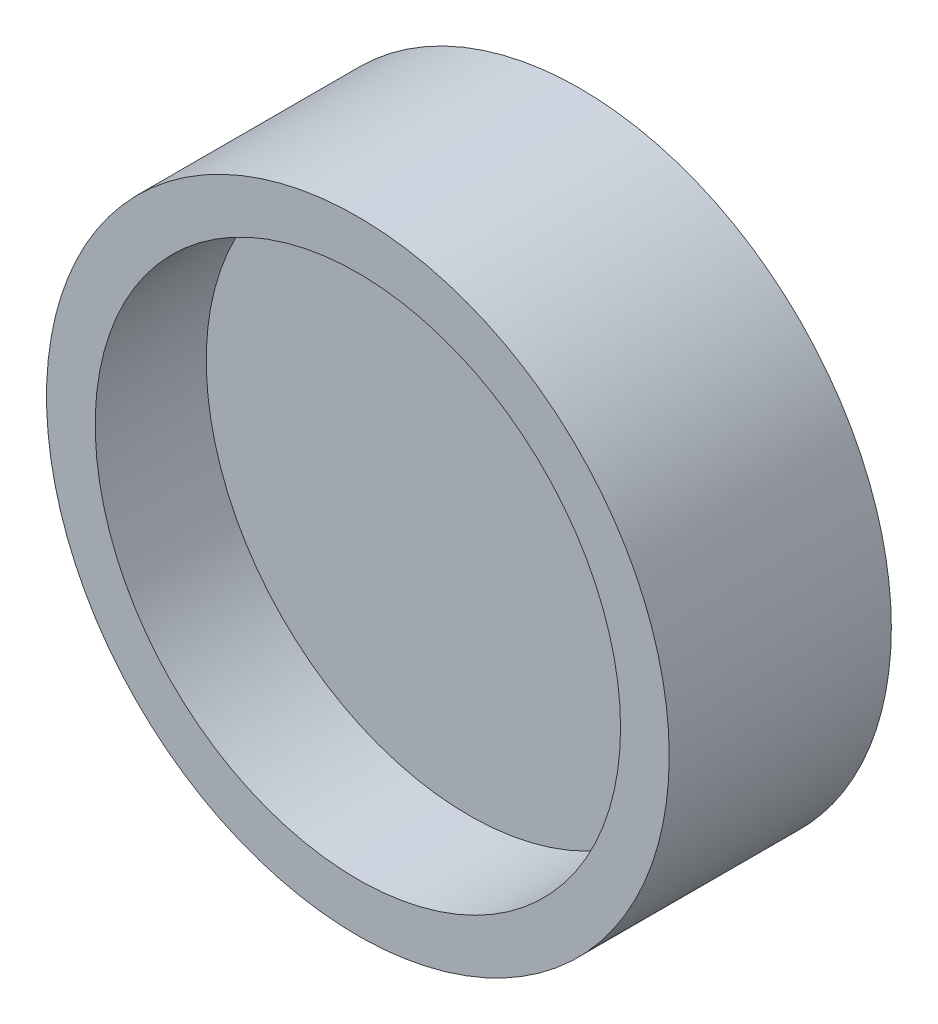
SolidWorks part; units mm, degrees
ref_plane "Front Plane" through (0, 0, 0) normal (0, 0, 1) x (1, 0, 0)
ref_plane "Top Plane" through (0, 0, 0) normal (0, 1, 0) x (1, 0, 0)
ref_plane "Right Plane" through (0, 0, 0) normal (1, 0, 0) x (0, 0, -1)
sketch "Body Circle" plane through (0, 0, 0) normal (0, 0, 1) x (1, 0, 0)
  line L0 (0, -24.95) -> (0, 24.95) construction
  circle A0 centre (0, 0) radius 24.95
  point P14 (0, 0)
extrude "Body" add sketch "Body Circle" along normal blind 17.8 contours A0
sketch "Inner Face Circle Sketch" plane through (0, 0, 17.8) normal (0, 0, 1) x (1, 0, 0)
  circle A0 centre (0, 0) radius 21.05
extrude "Inner Face" cut sketch "Inner Face Circle Sketch" against normal blind 8.9
sketch "Back Circle Sketch" plane through (0, 0, 0) normal (0, 0, -1) x (-1, 0, 0)
  line L0 (0, -26.5965) -> (0, 26.5965) construction
  line L1 (0, -19.9374) -> (-15, -19.9374) construction
  line L2 (-15, -19.9374) -> (-21.098, -13.3182) construction
  line L3 (-36.098, -33.2556) -> (0, 0) construction
  line L4 (-1.672, -23.3354) -> (-23.394, 0.2432) construction
  line L5 (-21.098, -13.3182) -> (-15.582, -8.2365)
  line L6 (11.5, 8.45) -> (0, 8.45) construction
  line L7 (-15, -19.9374) -> (-9.484, -14.8557)
  line L8 (-28.3873, 24.95) -> (28.3873, 24.95) construction
  line L9 (2.8283, -22.2891) -> (2.8283, -24.7891)
  line L10 (-2.8283, -22.2891) -> (-2.8283, -24.7891)
  line L11 (-32.3874, 0) -> (32.3874, 0) construction
  line L12 (2.8283, 22.2891) -> (2.8283, 24.7891)
  line L13 (-2.8283, 22.2891) -> (-2.8283, 24.7891)
  arc A0 (-15, -19.9374) -> (-2.8283, -24.7891) centre (0, 0) ccw
  circle A1 centre (0, 0) radius 24.95 construction
  arc A2 (-9.484, -14.8557) -> (-15.582, -8.2365) centre (-12.533, -11.5461) ccw
  circle A3 centre (11.5, 8.45) radius 4.5
  arc A4 (2.8283, -22.2891) -> (-2.8283, -22.2891) centre (0, -22.2891) ccw
  arc A5 (2.8283, -24.7891) -> (2.8283, 24.7891) centre (0, 0) ccw
  circle A6 centre (6.5, -13.95) radius 6.5
  arc A7 (2.8283, 22.2891) -> (-2.8283, 22.2891) centre (0, 22.2891) cw
  arc A8 (-2.8283, 24.7891) -> (-21.098, -13.3182) centre (0, 0) ccw
  point P8 (0, 0)
  point P14 (-18.049, -16.6278)
  point P16 (-12.533, -11.5461)
  point P24 (0, 24.95)
  point P35 (0, 0)
  point P42 (-23.6326, 0)
  point P44 (-21.8205, 0)
  point P45 (-22.2388, 0)
  dimension "D4" = 11.5
  dimension "D6" = 9
  dimension "D7" = 6.5
  dimension "D1" = 15
  dimension "D2" = 9
  dimension "D3" = 7.5
  dimension "D5" = 16.5
  dimension "D8" = 38.9
extrude "Back" add sketch "Back Circle Sketch" along normal blind 1.5
sketch "Rectangle Hole Sketch" plane through (0, 0, -1.5) normal (0, 0, -1) x (-1, 0, 0)
  line L8 (0, 0) -> (-28.5549, -26.3064) construction
  line L10 (-9.484, -14.8557) -> (-15, -19.9374) construction
  line L11 (-17.3135, -15.9502) -> (-14.6033, -18.8921)
  line L12 (-14.6033, -18.8921) -> (-13.5001, -17.8758)
  line L13 (-13.5001, -17.8758) -> (-16.2103, -14.9339)
  line L14 (-16.2103, -14.9339) -> (-17.3135, -15.9502)
  arc A1 (-9.484, -14.8557) -> (-15.582, -8.2365) centre (-12.533, -11.5461) ccw construction
  dimension "D1" = 1.5
  dimension "D2" = 4
  dimension "D3" = 5
extrude "Rectangle Hole" cut sketch "Rectangle Hole Sketch" against normal blind 5
pattern_circular "Rectangle Hole Pattern" count 4 over 360 about axis through (0, 0, 17.8) along (0, 0, -1) of "Rectangle Hole"
chamfer "Back Chamfer" distance 1.5 angle 60 7 edges at (-24.95, 0, -1.5) (-16, 8.45, -1.5) (9.2384, -23.1766, -1.5) (12.242, -17.3966, -1.5) (9.2234, -8.4971, -1.5) (18.34, -10.7773, -1.5) (22.498, 10.7861, -1.5) first distance on face at (24.95, 0, 17.8) first distance on face at (-16.913, -15.4068, -1.5) first distance on face at (12.242, -17.3966, -0.75) first distance on face at (10.8782, -10.0216, -0.75) first distance on face at (18.34, -10.7773, -0.75)
sketch "Alarm Switch Slot Sketch" plane through (0, 0, 0) normal (0, 0, 1) x (1, 0, 0)
  line L0 (-36.0088, 0) -> (36.0088, 0) construction
  line L1 (23.7482, -7.65) -> (23.7482, 7.65) construction
  line L2 (0, 0) -> (23.7482, 7.65) construction
  line L3 (0, 0) -> (23.7482, -7.65) construction
  line L4 (23.7482, 7.65) -> (21.2753, 6.8534)
  line L5 (23.7482, -7.65) -> (21.2753, -6.8534)
  arc A1 (21.098, -13.3182) -> (2.8283, 24.7891) centre (0, 0) ccw construction
  arc A2 (23.7482, 7.65) -> (23.7482, -7.65) centre (0, 0) cw
  arc A3 (21.2753, 6.8534) -> (21.2753, -6.8534) centre (0, 0) cw
  arc A4 (20.3976, -9.1403) -> (17.6671, 13.6924) centre (0, 0) ccw construction
  point P4 (0, 0)
  point P8 (23.7482, 0)
  point P14 (24.95, 0)
  point P18 (22.3519, 0)
  dimension "D1" = 7.65
extrude "Alarm Switch Slot" cut sketch "Alarm Switch Slot Sketch" against normal through all contours A3 L5 A2 L4
sketch "Alarm Switch Body Slot Sketch" plane through (0, 0, 0) normal (0, 0, 1) x (1, 0, 0)
  line L0 (0, 0) -> (24.95, 0) construction
  line L1 (23.7482, 7.65) -> (23.7482, -7.65) construction
  line L2 (24.6256, 4.01) -> (-1, 1)
  line L3 (-1, 1) -> (-1, -1)
  line L4 (-1, -1) -> (24.6256, -4.01)
  arc A0 (23.7482, -7.65) -> (23.7482, 7.65) centre (0, 0) ccw construction
  arc A1 (24.6256, -4.01) -> (24.6256, 4.01) centre (0, 0) ccw
  circle A2 centre (0, 0) radius 0.5
  point P12 (-1, 0)
  dimension "D1" = 3.64
  dimension "D2" = 3.64
  dimension "D3" = 2
  dimension "D4" = 1
extrude "Alarm Switch Body Slot" cut sketch "Alarm Switch Body Slot Sketch" against normal blind 1
sketch "Dial Stand Circle" plane through (0, 0, 0) normal (0, 0, 1) x (1, 0, 0)
  circle A0 centre (12.533, -11.5461) radius 0.5
  circle A1 centre (-11.5, 8.45) radius 0.5
  circle A2 centre (-11.5, 8.45) radius 5.134 construction
  arc A3 (15.582, -8.2365) -> (9.484, -14.8557) centre (12.533, -11.5461) ccw construction
extrude "Dial Stands" add sketch "Dial Stand Circle" against normal blind 1
sketch "Battery Lid Hole Circle" plane through (0, 0, 0) normal (0, 0, -1) x (-1, 0, 0)
  circle A0 centre (6.5, -13.95) radius 5.9
extrude "Battery Lid Hole" cut sketch "Battery Lid Hole Circle" against normal blind 1.5
sketch "Lid Lock Notch Hole Sketch" plane through (0, 0, 0) normal (0, 0, 1) x (1, 0, 0)
  line L0 (-8.3521, -7.7195) -> (-4.6479, -7.7195) construction
  line L1 (-4.6479, -7.7195) -> (-4.6479, -8.3483)
  line L2 (-8.3521, -7.7195) -> (-8.3521, -8.3483)
  circle A0 centre (-6.5, -13.95) radius 6.5 construction
  arc A1 (-4.6479, -7.7195) -> (-8.3521, -7.7195) centre (-6.5, -13.95) ccw
  circle A2 centre (-6.5, -13.95) radius 5.9 construction
  arc A3 (-4.6479, -8.3483) -> (-8.3521, -8.3483) centre (-6.5, -13.95) ccw
  point P6 (-6.5, -7.7195)
extrude "Battery Lid Lock Notch Hole" cut sketch "Lid Lock Notch Hole Sketch" along normal blind 1.5
sketch "Lid Lock Notch Plane Sketch" plane through (0, 0, 0) normal (0, 0, 1) x (1, 0, 0)
  line L0 (-14.175, -13.95) -> (1.175, -13.95) construction
  point P4 (-6.5, -13.95)
ref_plane "Lid Lock Notch Plane" through (0, -13.95, 0) normal (0, -1, 0) x (1, 0, 0)
mirror "Lid Lock Notch Mirror" about plane through (0, -13.95, 0) normal (0, -1, 0) of "Battery Lid Lock Notch Hole"
sketch "Lid Lock Ridge Circle " plane through (0, 0, 1.5) normal (0, 0, -1) x (-1, 0, 0)
  circle A0 centre (6.5, -13.95) radius 6.5 construction
  circle A1 centre (6.5, -13.95) radius 6.5
extrude "Lid Lock Ridge" cut sketch "Lid Lock Ridge Circle " along normal blind 0.5
sketch "Screw Hole Circles" plane through (0, 0, 0) normal (0, 0, 1) x (1, 0, 0)
  circle A0 centre (0, 22.2891) radius 0.7
  circle A1 centre (0, -22.2891) radius 0.7
  dimension "D1" = 1.4
extrude "Screw Holes" cut sketch "Screw Hole Circles" along normal blind 5.5
sketch "On/Off Text Sketch" plane through (0, 0, -1.5) normal (0, 0, -1) x (-1, 0, 0)
  line L0 (-20.9169, -6.1559) -> (-17.9382, -6.1559) construction
  line L1 (-20.9169, 6.0235) -> (-17.9382, 6.0235) construction
  text T0 "ON" font "Times New Roman" height 1
  text T1 "OFF" font "Times New Roman" height 1
extrude "On/Off Text Indent" cut sketch "On/Off Text Sketch" against normal blind 0.1
sketch "Open/Close Text Sketch" plane through (0, 0, -1.5) normal (0, 0, -1) x (-1, 0, 0)
  line L0 (6.5, -13.95) -> (24.0506, -13.95) construction
  line L1 (6.5, -13.95) -> (6.5, 3.3393) construction
  arc A0 (15.5, -13.95) -> (6.5, -4.95) centre (6.5, -13.95) ccw construction
  text T0 "OPEN" font "Times New Roman" height 1
  text T1 "CLOSE" font "Times New Roman" height 1
  dimension "D1" = 18
extrude "Open/Close Text Indent" cut sketch "Open/Close Text Sketch" against normal blind 0.1
sketch "Open Arrow Sketch" plane through (0, 0, -1.5) normal (0, 0, -1) x (-1, 0, 0)
  line L0 (7.3396, -5.5984) -> (9.2916, -6.0342)
  line L1 (9.2916, -6.0342) -> (7.9382, -7.5067)
  line L2 (7.9382, -7.5067) -> (7.3396, -5.5984)
  line L3 (11.5, 8.45) -> (6.5, -13.95) construction
  point P8 (8.3156, -5.8163)
  dimension "D1" = 2
extrude "Open Arrow Indent" cut sketch "Open Arrow Sketch" against normal blind 0.1
sketch "Close Arrow Sketch" plane through (0, 0, -1.5) normal (0, 0, -1) x (-1, 0, 0)
  line L0 (6.5, -13.95) -> (26.1561, -8.565) construction
  line L1 (14.8256, -12.706) -> (14.2971, -10.7771)
  line L2 (14.2971, -10.7771) -> (12.8908, -12.1992)
  line L3 (12.8908, -12.1992) -> (14.8256, -12.706)
  point P6 (14.5613, -11.7415)
  dimension "D1" = 2
  dimension "D2" = 0.6
extrude "Close Arrow Indent" cut sketch "Close Arrow Sketch" against normal blind 0.1
sketch "Alarm Time Bell + Arrow Sketch" plane through (0, 0, -1.5) normal (0, 0, -1) x (-1, 0, 0)
  line L0 (-12.533, -11.5461) -> (-25.7677, 6.4983) construction
  line L1 (-12.533, -11.5461) -> (26.2294, -11.5461) construction
  line L2 (-12.533, -11.5461) -> (-12.533, 7.1792) construction
  line L3 (-12.533, -11.5461) -> (-16.1097, 7.1914) construction
  line L4 (2.4885, -3.5461) -> (-27.5545, -3.5461) construction
  line L5 (-12.533, -11.5461) -> (-8.9788, 7.0731) construction
  line L6 (-17.8558, -4.2889) -> (-17.2644, -5.0952)
  line L7 (-14.2205, -2.7057) -> (-14.033, -3.688)
  line L8 (-10.8455, -2.7057) -> (-11.033, -3.688)
  line L9 (-4.533, -11.5461) -> (-3.3637, -8.9293)
  line L10 (-3.3637, -8.9293) -> (-3.9218, -8.9293)
  line L11 (-13.6083, -3.5461) -> (-12.8986, -3.5461)
  line L12 (-13.7625, -3.2187) -> (-13.533, -2.941)
  line L13 (-11.533, -2.941) -> (-11.3035, -3.2187)
  line L14 (-13.533, -2.7057) -> (-11.533, -2.7057) construction
  line L15 (-13.533, -2.941) -> (-13.533, -1.941)
  line L16 (-11.533, -2.941) -> (-11.533, -1.941)
  line L17 (-12.0986, -3.5461) -> (-11.4577, -3.5461)
  arc A0 (-4.533, -11.5461) -> (-11.033, -3.688) centre (-12.533, -11.5461) ccw
  arc A1 (-3.9218, -8.9293) -> (-10.8455, -2.7057) centre (-12.533, -11.5461) ccw
  arc A2 (-14.2205, -2.7057) -> (-17.8558, -4.2889) centre (-12.533, -11.5461) ccw
  circle A3 centre (-12.533, -11.5461) radius 8 construction
  circle A4 centre (-12.533, -11.5461) radius 9 construction
  arc A5 (-14.033, -3.688) -> (-17.2644, -5.0952) centre (-12.533, -11.5461) ccw
  arc A6 (-11.4577, -3.5461) -> (-11.3035, -3.2187) centre (-11.4577, -3.3461) ccw
  arc A7 (-13.6083, -3.5461) -> (-13.7625, -3.2187) centre (-13.6083, -3.3461) cw
  arc A8 (-13.533, -1.941) -> (-11.533, -1.941) centre (-12.533, -1.941) cw
  arc A9 (-12.8986, -3.5461) -> (-12.0986, -3.5461) centre (-12.4986, -3.5461) ccw
  point P1 (-3.533, -11.5461)
  point P10 (-12.533, -3.5461)
  point P13 (-4.8825, -9.2071)
  point P28 (-12.533, -3.5461)
  point P30 (-11.033, -3.5461)
  point P33 (-14.033, -3.5461)
  point P37 (-12.533, -2.7057)
  dimension "D1" = 16
  dimension "D6" = 0.2
  dimension "D8" = 0.4
  dimension "D2" = 1.5
  dimension "D3" = 1.5
  dimension "D5" = 3
  dimension "D7" = 1
  dimension "D4" = 1
extrude "Alarm Time Bell + Arrow" cut sketch "Alarm Time Bell + Arrow Sketch" against normal blind 0.1
sketch "Current Time Symbol + Arrow Sketch" plane through (0, 0, -1.5) normal (0, 0, -1) x (-1, 0, 0)
  line L0 (11.5, 8.45) -> (6.5552, -0.1147) construction
  line L1 (11.5, 8.45) -> (2.9365, 17.0135) construction
  line L2 (11.5, 8.45) -> (-3.0297, 8.45) construction
  line L3 (11.5, 8.45) -> (-2.5602, 12.3894) construction
  line L4 (5.9669, 13.983) -> (6.674, 13.2759)
  line L6 (4.6757, 8.5401) -> (3.7075, 7.7378)
  line L7 (4.9993, 10.5284) -> (4.1777, 11.2093)
  line L8 (8.0875, 2.5394) -> (5.4928, 2.5394)
  line L9 (5.4928, 2.5394) -> (5.9223, 2.9619)
  line L10 (4.7576, 10.3391) -> (3.2177, 11.6153)
  line L11 (3.2177, 11.6153) -> (2.7073, 10.9993)
  line L12 (2.7073, 10.9993) -> (4.2471, 9.7231)
  line L13 (4.2471, 9.7231) -> (4.7576, 10.3391)
  line L14 (4.7576, 8.9977) -> (1.6779, 6.4452)
  line L15 (1.6779, 6.4452) -> (1.1674, 7.0612)
  line L16 (1.1674, 7.0612) -> (4.2471, 9.6136)
  line L17 (4.2471, 9.6136) -> (4.7576, 8.9977)
  arc A0 (6.674, 13.2759) -> (4.9993, 10.5284) centre (11.5, 8.45) ccw
  arc A1 (5.9669, 13.983) -> (4.1777, 11.2093) centre (11.5, 8.45) ccw
  arc A2 (3.7075, 7.7378) -> (5.9223, 2.9619) centre (11.5, 8.45) ccw
  arc A3 (4.6757, 8.5401) -> (8.0875, 2.5394) centre (11.5, 8.45) ccw
  arc A4 (5.9669, 13.983) -> (7.5875, 1.6734) centre (11.5, 8.45) ccw construction
  arc A6 (6.674, 13.2759) -> (8.0875, 2.5394) centre (11.5, 8.45) ccw construction
  dimension "D1" = 0.3
  dimension "D2" = 45
  dimension "D3" = 60
  dimension "D5" = 0.8
  dimension "D6" = 2
  dimension "D7" = 4
  dimension "D8" = 0.3
  dimension "D4" = 1
extrude "Current Time Symbol + Arrow" cut sketch "Current Time Symbol + Arrow Sketch" against normal blind 0.1
